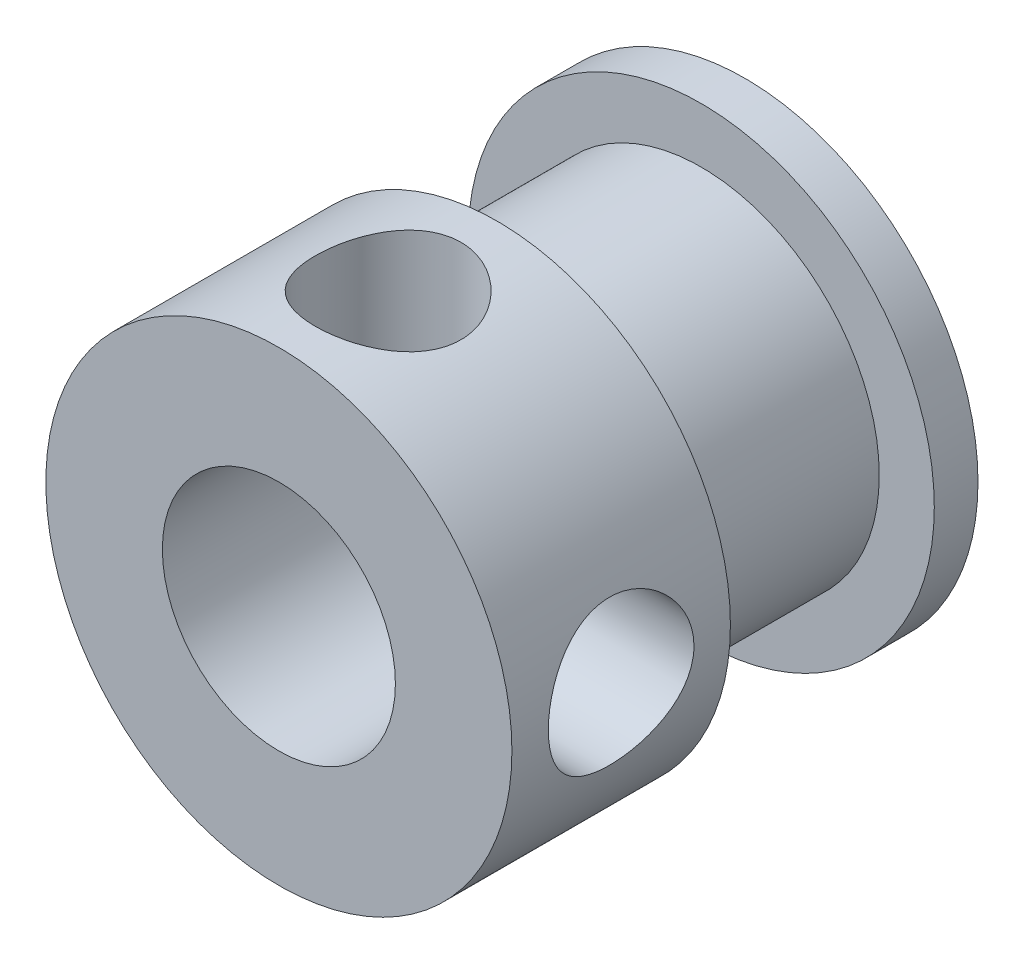
SolidWorks part; units mm, degrees
ref_plane "Front Plane" through (0, 0, 0) normal (0, 0, 1) x (1, 0, 0)
ref_plane "Top Plane" through (0, 0, 0) normal (0, 1, 0) x (1, 0, 0)
ref_plane "Right Plane" through (0, 0, 0) normal (1, 0, 0) x (0, 0, -1)
sketch "Sketch1" plane through (0, 0, 0) normal (0, 0, 1) x (1, 0, 0)
  circle A0 centre (0, 0) radius 8
extrude "Boss-Extrude1" add sketch "Sketch1" along normal blind 1.5
sketch "Sketch2" plane through (0, 0, 1.5) normal (0, 0, 1) x (1, 0, 0)
  circle A0 centre (0, 0) radius 6.11
extrude "Boss-Extrude2" add sketch "Sketch2" along normal blind 7
sketch "Sketch4" plane through (0, 0, 8.5) normal (0, 0, 1) x (1, 0, 0)
  circle A0 centre (0, 0) radius 8
extrude "Boss-Extrude4" add sketch "Sketch4" along normal blind 7.5
sketch "Sketch6" plane through (0, 0, 16) normal (0, 0, 1) x (1, 0, 0)
  circle A0 centre (0, 0) radius 4
extrude "Cut-Extrude1" cut sketch "Sketch6" against normal up to surface (16 mm away) up to face at (8, 0, 0)
ref_axis "Axis1" through (0, 0, 0) along (0, 0, 1)
ref_plane "Plane1" through (0, 0, 0) normal (-1, 0, 0) x (0, 0, 1)
sketch "Sketch7" plane through (0, 0, 0) normal (-1, 0, 0) x (0, 0, 1)
  line L0 (16, 0) -> (12.25, 0) construction
  line L1 (16, -8) -> (16, 8) construction
  line L2 (0, 0) -> (16, 0) construction
  circle A0 centre (12.25, 0) radius 2.5
extrude "Cut-Extrude2" cut sketch "Sketch7" against normal up to surface (8 mm away) up to face at (8, 0, 16)
ref_plane "Plane2" through (0, 0, 0) normal (0, -1, 0) x (0, 0, 1)
sketch "Sketch8" plane through (0, 0, 0) normal (0, -1, 0) x (0, 0, 1)
  line L0 (16, 0) -> (12.25, 0) construction
  line L1 (16, -8) -> (16, 8) construction
  line L2 (11, 0) -> (-11, 0) construction
  circle A0 centre (12.25, 0) radius 2.5
extrude "Cut-Extrude3" cut sketch "Sketch8" against normal up to surface (8 mm away) up to face at (7.9878, 0.4424, 9.7894)
